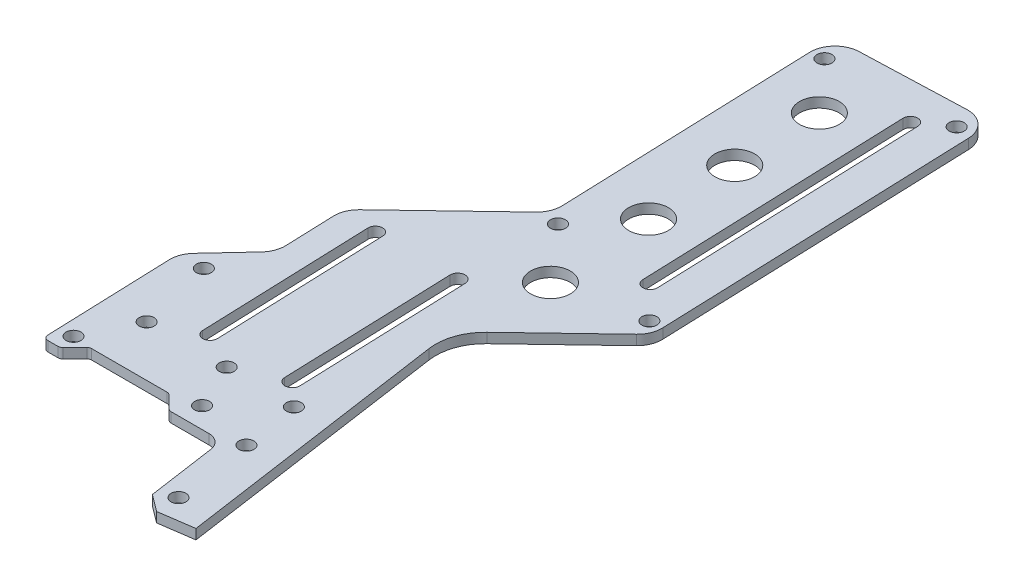
SolidWorks part; units mm, degrees
ref_plane "前视基准面" through (0, 0, 0) normal (0, 0, 1) x (1, 0, 0)
ref_plane "上视基准面" through (0, 0, 0) normal (0, 1, 0) x (1, 0, 0)
ref_plane "右视基准面" through (0, 0, 0) normal (1, 0, 0) x (0, 0, -1)
sketch "Sketch1" plane through (0, 0, 0) normal (0, 1, 0) x (1, 0, 0)
  line L6 (35.9461, 32.5892) -> (55.0686, 50.8364)
  line L7 (56.6136, 54.6329) -> (54.3224, 118.5515)
  line L8 (49.1465, 123.3692) -> (28.1497, 122.6166)
  line L9 (-4.0536, -9.5444) -> (-0.7001, -9.5444)
  line L10 (-0.7001, -9.5444) -> (2.2999, -6.5444)
  line L11 (18.2999, -6.5444) -> (2.2999, -6.5444)
  line L12 (26.2999, -9.5444) -> (21.2999, -9.5444)
  line L13 (18.2999, -6.5444) -> (21.2999, -9.5444)
  line L14 (23.3321, 117.4407) -> (25.1817, 65.8404)
  line L15 (23.6367, 62.044) -> (5.4762, 44.7149)
  line L16 (3.9312, 40.9184) -> (4.2853, 31.0397)
  line L17 (2.9485, 27.454) -> (-3.6599, 20.3542)
  line L18 (-4.9968, 16.7685) -> (-4.0536, -9.5444)
  line L19 (26.2999, -9.5444) -> (28.2999, -9.5444)
  line L20 (28.2999, -9.5444) -> (29.3174, -9.5444)
  line L21 (32.2867, -12.1163) -> (34.2711, -25.8807)
  line L22 (40.206, 3.0407) -> (35.9461, 32.5892)
  line L23 (40.206, 3.0407) -> (44.5979, -27.4229)
  line L24 (44.5979, -27.4229) -> (37.6684, -28.4219)
  line L26 (34.2711, -25.8807) -> (37.6684, -28.4219)
  arc A2 (55.0686, 50.8364) -> (56.6136, 54.6329) centre (51.6168, 54.4537) ccw
  arc A3 (-3.6599, 20.3542) -> (-4.9968, 16.7685) centre (0, 16.9476) ccw
  circle A4 centre (23.7704, -5.3703) radius 1.5
  circle A5 centre (19.5405, 3.8264) radius 1.5
  circle A6 centre (-1.2805, -6.2266) radius 1.5
  circle A7 centre (3.5641, 3.664) radius 1.5
  arc A8 (4.2853, 31.0397) -> (2.9485, 27.454) centre (-0.7115, 30.8606) cw
  arc A9 (5.4762, 44.7149) -> (3.9312, 40.9184) centre (8.928, 41.0975) ccw
  arc A10 (25.1817, 65.8404) -> (23.6367, 62.044) centre (20.1849, 65.6613) cw
  arc A11 (54.3224, 118.5515) -> (49.1465, 123.3692) centre (49.3257, 118.3724) ccw
  arc A12 (28.1497, 122.6166) -> (23.3321, 117.4407) centre (28.3289, 117.6198) ccw
  arc A13 (29.3174, -9.5444) -> (32.2867, -12.1163) centre (29.3174, -12.5444) cw
  dimension "D3" = 3
  dimension "D2" = 135
extrude "Boss-Extrude1" add sketch "Sketch1" along normal blind 2
sketch "Sketch2" plane through (0, 0, 0) normal (0, -1, 0) x (1, 0, 0)
  line L16 (10.9319, -42.3885) -> (12.1697, -7.8569) construction
  line L19 (9.4767, -42.3363) -> (10.7145, -7.8047)
  line L22 (12.3872, -42.4407) -> (13.625, -7.9091)
  line L25 (27.4452, -42.4518) -> (28.683, -7.9202) construction
  line L26 (25.9469, -42.3981) -> (27.1847, -7.8665)
  line L27 (28.9435, -42.5055) -> (30.1813, -7.9739)
  line L32 (45.6918, -115.4691) -> (47.6415, -61.0787) construction
  line L33 (44.2395, -115.4171) -> (46.1892, -61.0266)
  line L34 (47.1441, -115.5212) -> (49.0938, -61.1307)
  arc A16 (9.4767, -42.3363) -> (12.3872, -42.4407) centre (10.9319, -42.3885) ccw
  arc A17 (13.625, -7.9091) -> (10.7145, -7.8047) centre (12.1697, -7.8569) ccw
  arc A18 (25.9469, -42.3981) -> (28.9435, -42.5055) centre (27.4452, -42.4518) ccw
  arc A19 (30.1813, -7.9739) -> (27.1847, -7.8665) centre (28.683, -7.9202) ccw
  arc A24 (44.2395, -115.4171) -> (47.1441, -115.5212) centre (45.6918, -115.4691) ccw
  arc A25 (49.0938, -61.1307) -> (46.1892, -61.0266) centre (47.6415, -61.0787) ccw
  circle A34 centre (34.8935, -107.9094) radius 4
  circle A35 centre (35.5006, -90.2447) radius 4
  circle A36 centre (37.3756, -51.2344) radius 4
  circle A37 centre (36.1937, -72.1788) radius 4
  point P2 (37.3756, -51.2344)
  point P19 (46.6667, -88.2739)
  point P38 (11.5508, -25.1227)
  point P45 (28.0641, -25.186)
  point P75 (30.6759, -3.7668)
extrude "Cut-Extrude1" cut sketch "Sketch2" against normal through all
sketch "Sketch3" plane through (0, 2, 0) normal (0, 1, 0) x (1, 0, 0)
  line L0 (25.9434, 117.8711) -> (27.9394, 62.1871) construction
  line L1 (30.8545, 56.6616) -> (28.7528, 115.2921) construction
  circle A0 centre (0, 18.7605) radius 1.5
  circle A1 centre (54.0546, 54.4882) radius 1.5
  circle A2 centre (25.9434, 117.8711) radius 1.5
  circle A3 centre (51.146, 119.3117) radius 1.5
  circle A4 centre (27.9394, 62.1871) radius 1.5
  circle A5 centre (33.2404, 3.6609) radius 1.5
extrude "Cut-Extrude2" cut sketch "Sketch3" against normal blind 10
fillet "Fillet1" radius 10 1 edges at (35.9461, 1, -32.5892)
sketch "Sketch4" plane through (0, 0, 0) normal (0, -1, 0) x (1, 0, 0)
  arc A4 (36.8062, 22.4407) -> (37.2151, 25.2772) centre (37.4497, 23.7957) ccw
  arc A5 (37.2151, 25.2772) -> (36.8062, 22.4407) centre (37.4497, 23.7957) ccw
  arc A6 (34.9091, 9.282) -> (34.5002, 6.4455) centre (35.1437, 7.8004) ccw
  arc A7 (34.5002, 6.4455) -> (34.9091, 9.282) centre (35.1437, 7.8004) ccw
extrude "Cut-Extrude3" cut sketch "Sketch4" against normal blind 23
fillet "Fillet2" radius 1 5 edges at (21.2999, 1, 9.5444) (18.2999, 1, 6.5444) (2.2999, 1, 6.5444) (-0.7001, 1, 9.5444) (-4.0536, 1, 9.5444)
